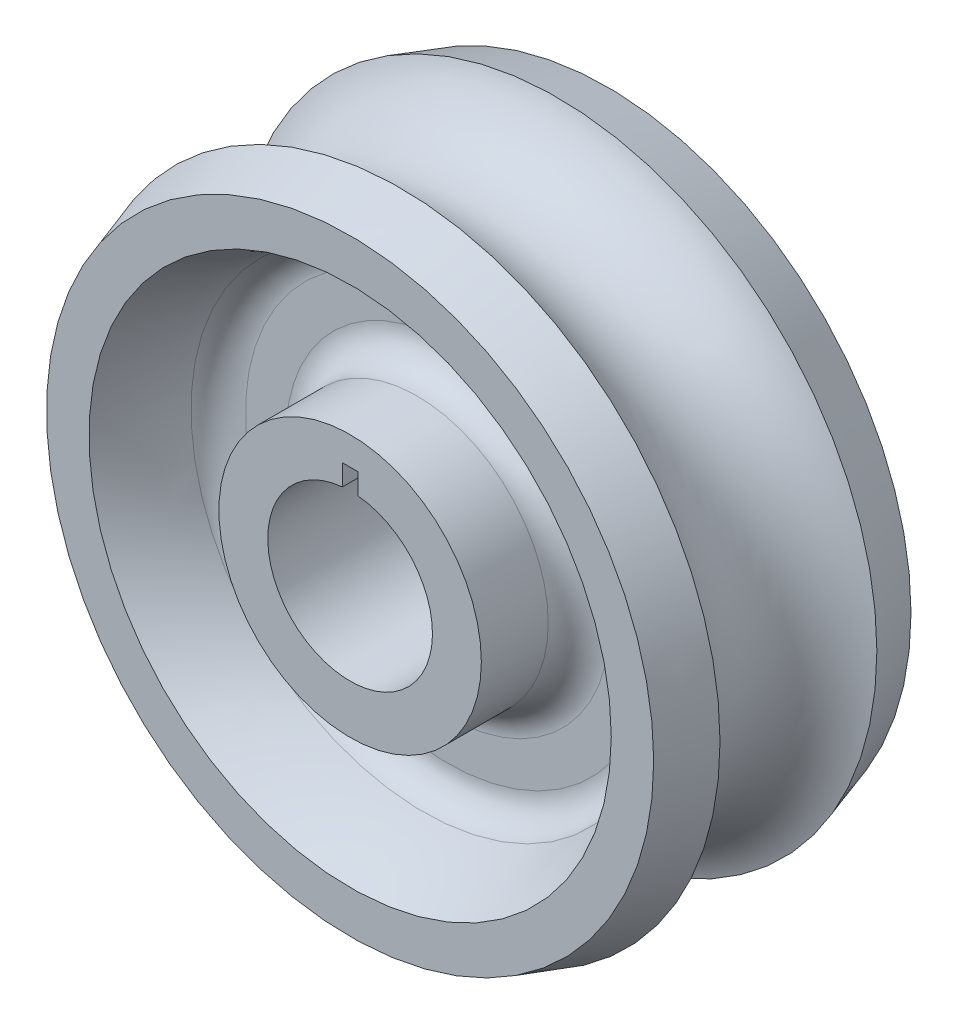
SolidWorks part; units mm, degrees
material "PW20:29:Sc:0:"
ref_plane "Front" through (0, 0, 0) normal (0, 0, 1) x (1, 0, 0)
ref_plane "Top" through (0, 0, 0) normal (0, 1, 0) x (1, 0, 0)
ref_plane "Right" through (0, 0, 0) normal (1, 0, 0) x (0, 0, -1)
sketch "Sketch1" plane through (0, 0, 0) normal (1, 0, 0) x (0, 0, -1)
  line L0 (0, 0) -> (159.8623, 0) construction
  line L1 (0, 0) -> (0, 93.2897) construction
  line L2 (-12.5, 8) -> (12.5, 8)
  line L3 (12.5, 8) -> (12.5, 12.75)
  line L4 (12.5, 12.75) -> (6, 12.75)
  line L5 (3, 15.75) -> (3, 19.676)
  line L6 (12.5, 25.375) -> (12.5, 29.5)
  line L7 (12.5, 29.5) -> (7.6194, 31.0618)
  line L8 (-12.5, 29.5) -> (-7.6194, 31.0618)
  line L9 (-12.5, 25.375) -> (-12.5, 29.5)
  line L10 (-3, 15.75) -> (-3, 19.676)
  line L11 (-12.5, 12.75) -> (-6, 12.75)
  line L12 (-12.5, 8) -> (-12.5, 12.75)
  arc A0 (6, 12.75) -> (3, 15.75) centre (6, 15.75) cw
  arc A1 (3, 19.676) -> (5.3571, 22.6064) centre (6, 19.676) cw
  arc A2 (5.3571, 22.6064) -> (12.5, 25.375) centre (0, 47.0256) ccw
  arc A3 (7.6194, 31.0618) -> (-7.6194, 31.0618) centre (0, 33.5) cw
  arc A4 (-5.3571, 22.6064) -> (-12.5, 25.375) centre (0, 47.0256) cw
  arc A5 (-3, 19.676) -> (-5.3571, 22.6064) centre (-6, 19.676) ccw
  arc A6 (-6, 12.75) -> (-3, 15.75) centre (-6, 15.75) ccw
  point P29 (0, 8)
  dimension "D1" = 25
  dimension "D2" = 3
  dimension "D4" = 8
  dimension "D9" = 25
  dimension "D3" = 50.75
  dimension "D5" = 6
  dimension "D6" = 4.75
  dimension "D7" = 16
  dimension "D8" = 21.5
  dimension "D10" = 67
revolve "Base-Revolve" add sketch "Sketch1" angle 360 about L0
sketch "Sketch2" plane through (0, 0, 12.5) normal (0, 0, 1) x (1, 0, 0)
  line L0 (0, 0) -> (0, 10.5711) construction
  line L1 (-0.75, 7.9648) -> (-0.75, 10)
  line L2 (0.75, 7.9648) -> (0.75, 10)
  line L3 (-0.75, 10) -> (0.75, 10)
  circle A0 centre (0, 0) radius 8 construction
  arc A1 (0.75, 7.9648) -> (-0.75, 7.9648) centre (0, 0) ccw
  dimension "D1" = 1.5
  dimension "D2" = 10
extrude "Cut-Extrude1" cut sketch "Sketch2" against normal through all
ref_axis "Worm CL" through (0, 0, 50) along (0, 0, -1)
